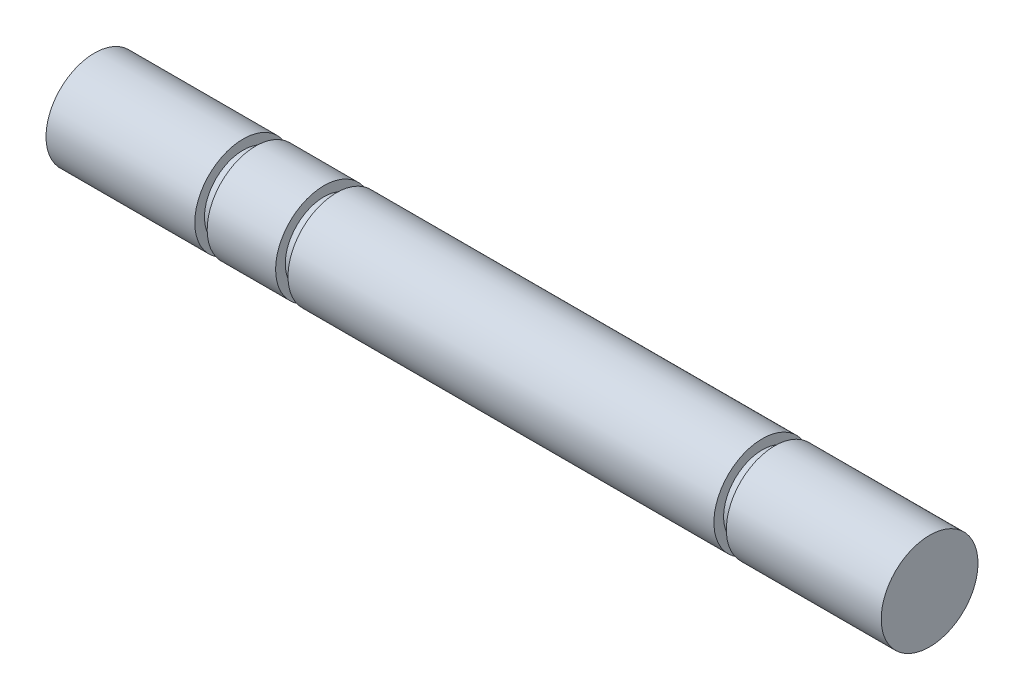
SolidWorks part; units mm, degrees
material "Plain Carbon Steel"
ref_plane "Front Plane" through (0, 0, 0) normal (0, 0, 1) x (1, 0, 0)
ref_plane "Top Plane" through (0, 0, 0) normal (0, 1, 0) x (1, 0, 0)
ref_plane "Right Plane" through (0, 0, 0) normal (1, 0, 0) x (0, 0, -1)
sketch "Sketch1" plane through (0, 0, 0) normal (1, 0, 0) x (0, 0, -1)
  circle A0 centre (0, 0) radius 2.5
  dimension "D1" = 5
extrude "Boss-Extrude1" add sketch "Sketch1" along normal blind 100
ref_plane "Plane1" through (92, 0, 0) normal (1, 0, 0) x (0, 0, -1)
sketch "Sketch2" plane through (92, 0, 0) normal (1, 0, 0) x (0, 0, -1)
  circle A0 centre (0, 0) radius 2
  circle A1 centre (0, 0) radius 2.5
  dimension "D1" = 4
  dimension "D2" = 5
extrude "Cut-Extrude1" cut sketch "Sketch2" against normal blind 0.64
ref_plane "Plane2" through (69.36, 0, 0) normal (1, 0, 0) x (0, 0, -1)
sketch "Sketch3" plane through (69.36, 0, 0) normal (1, 0, 0) x (0, 0, -1)
  circle A0 centre (0, 0) radius 2.5
  circle A1 centre (0, 0) radius 2
  dimension "D1" = 4
  dimension "D2" = 5
extrude "Cut-Extrude2" cut sketch "Sketch3" against normal blind 0.64
ref_plane "Plane3" through (56.86, 0, 0) normal (-1, 0, 0) x (0, 0, 1)
sketch "Sketch4" plane through (56.86, 0, 0) normal (-1, 0, 0) x (0, 0, 1)
  circle A0 centre (0, 0) radius 2.5
  dimension "D1" = 5
extrude "Cut-Extrude3" cut sketch "Sketch4" along normal up to surface (56.86 mm away) up to face at (0, 0, -2.5)
ref_plane "Plane4" through (65.185, 0, 0) normal (-1, 0, 0) x (0, 0, 1)
sketch "Sketch6" plane through (65.185, 0, 0) normal (-1, 0, 0) x (0, 0, 1)
  circle A0 centre (0, 0) radius 2
  circle A1 centre (0, 0) radius 2.5
  dimension "D1" = 5
  dimension "D2" = 4
extrude "Cut-Extrude4" cut sketch "Sketch6" along normal blind 0.64
